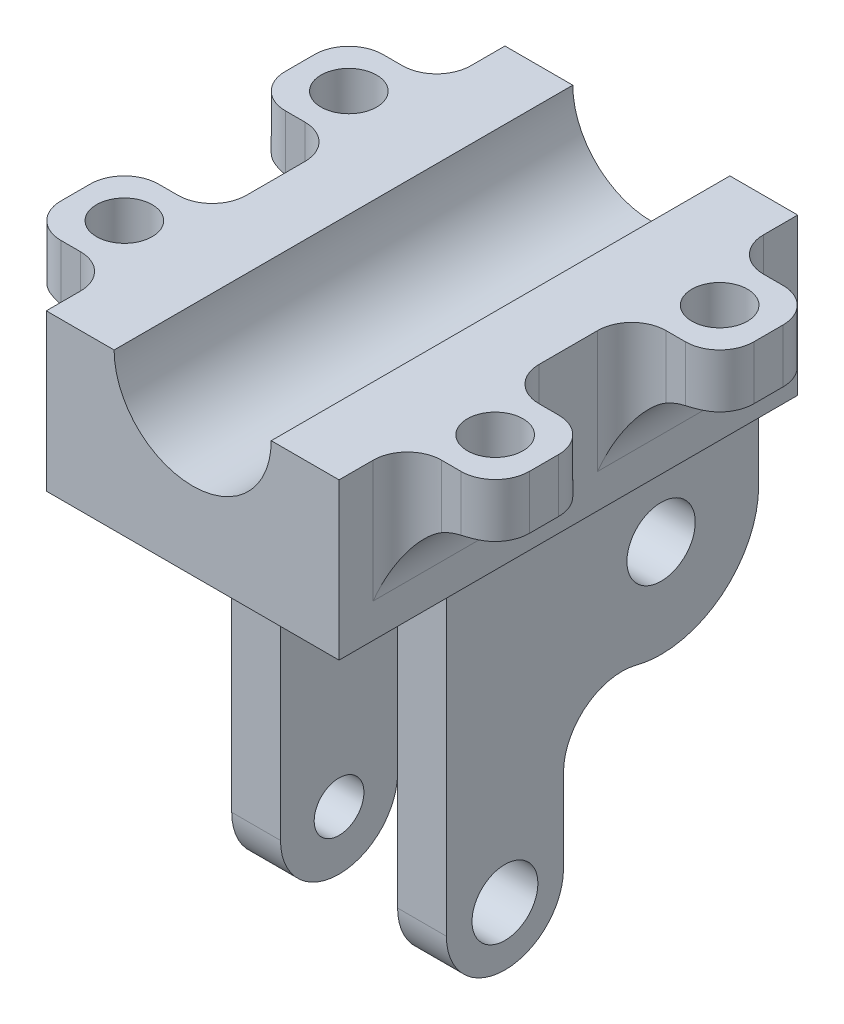
SolidWorks part; units mm, degrees
ref_plane "Front Plane" through (0, 0, 0) normal (0, 0, 1) x (1, 0, 0)
ref_plane "Top Plane" through (0, 0, 0) normal (0, 1, 0) x (1, 0, 0)
ref_plane "Right Plane" through (0, 0, 0) normal (1, 0, 0) x (0, 0, -1)
sketch "Sketch1" plane through (0, 0, 0) normal (0, 0, 1) x (1, 0, 0)
  line L1 (-15, -16) -> (15, -16)
  line L2 (-15, -16) -> (-15, 16)
  line L3 (-15, 16) -> (15, 16)
  line L4 (15, -16) -> (15, 16)
  line L5 (-15, -16) -> (15, 16) construction
  line L6 (-15, 16) -> (15, -16) construction
  circle A0 centre (0, 0) radius 8.05
  dimension "D1" = 16.1
  dimension "D2" = 30
  dimension "D3" = 32
extrude "Boss-Extrude1" add sketch "Sketch1" along normal blind 47
sketch "Sketch3" plane through (0, 0, 0) normal (0, 0, 1) x (1, 0, 0)
  line L0 (-15, 16) -> (-15, -16) construction
  line L1 (-15, 0) -> (15, 0)
  line L2 (-15, 0) -> (-15, 16)
  line L3 (-15, 16) -> (15, 16)
  line L4 (15, 0) -> (15, 16)
extrude "Cut-Extrude1" cut sketch "Sketch3" along normal through all both and the other way through all
sketch "Sketch4" plane through (0, 0, 0) normal (0, 1, 0) x (1, 0, 0)
  line L0 (15, -47) -> (15, 0) construction
  line L1 (15, -7) -> (24, -7)
  line L2 (15, -7) -> (15, -17)
  line L3 (15, -17) -> (24, -17)
  line L4 (24, -7) -> (24, -17)
  line L5 (8.05, 0) -> (15, 0) construction
  line L7 (0, 0) -> (0, 5.7091) construction
  line L15 (-24, -7) -> (-24, -17)
  line L16 (-15, -17) -> (-24, -17)
  line L17 (-15, -7) -> (-15, -17)
  line L18 (-15, -7) -> (-24, -7)
  line L19 (15, -23.5) -> (24.2871, -23.5) construction
  line L20 (-24, -40) -> (-24, -30)
  line L21 (-15, -30) -> (-24, -30)
  line L22 (-15, -40) -> (-15, -30)
  line L23 (-15, -40) -> (-24, -40)
  line L24 (15, -40) -> (15, -30)
  line L25 (15, -40) -> (24, -40)
  line L26 (15, -30) -> (24, -30)
  line L27 (24, -40) -> (24, -30)
  circle A0 centre (19, -12) radius 2.85
  circle A1 centre (19, -35) radius 2.85
  circle A2 centre (-19, -12) radius 2.85
  circle A3 centre (-19, -35) radius 2.85
  point P8 (24, -12)
  point P33 (24, -35)
  dimension "D4" = 5.7
  dimension "D1" = 10
  dimension "D2" = 9
  dimension "D3" = 7
extrude "Boss-Extrude2" add sketch "Sketch4" against normal blind 5.5
fillet "Fillet1" radius 3.5 16 edges at (15, -2.75, 17) (24, -2.75, 17) (24, -2.75, 7) (15, -2.75, 7) (-24, -2.75, 7) (-24, -2.75, 17) (-15, -2.75, 7) (-15, -2.75, 17) (24, -2.75, 30) (15, -2.75, 30) (24, -2.75, 40) (15, -2.75, 40) (-15, -2.75, 30) (-24, -2.75, 30) (-24, -2.75, 40) (-15, -2.75, 40)
fillet "Fillet2" radius 7 4 edges at (-15, -5.5, 12) (-15, -5.5, 35) (15, -5.5, 35) (15, -5.5, 12)
sketch "Sketch5" plane through (0, -16, 0) normal (0, -1, 0) x (1, 0, 0)
  line L0 (-15, 0) -> (15, 0) construction
  line L1 (-6, 0) -> (-11, 0)
  line L2 (-6, 0) -> (-6, 20)
  line L3 (-6, 20) -> (-11, 20)
  line L4 (-11, 0) -> (-11, 20)
  line L5 (-15, 47) -> (-15, 0) construction
  line L6 (0, 0) -> (0, 17.1726) construction
  line L7 (11, 0) -> (11, 20)
  line L8 (6, 20) -> (11, 20)
  line L9 (6, 0) -> (6, 20)
  line L10 (6, 0) -> (11, 0)
  dimension "D1" = 4
  dimension "D2" = 5
  dimension "D3" = 20
  dimension "D4" = 12
extrude "Boss-Extrude3" add sketch "Sketch5" along normal blind 20
sketch "Sketch6" plane through (11, 0, 0) normal (1, 0, 0) x (0, 0, -1)
  circle A0 centre (-10, -26) radius 3.5
  dimension "D1" = 7
extrude "Cut-Extrude2" cut sketch "Sketch6" against normal through all both and the other way through all
fillet "Fillet3" radius 10 4 edges at (-8.5, -36, 0) (-8.5, -36, 20) (8.5, -36, 20) (8.5, -36, 0)
fillet "Fillet4" radius 4 2 edges at (-11, -16, 10) (11, -16, 10)
sketch "Sketch7" plane through (0, -16, 0) normal (0, -1, 0) x (1, 0, 0)
  line L0 (0, 0) -> (0, 21.1072) construction
  line L1 (-11, 20) -> (-6, 20)
  line L2 (-11, 20) -> (-11, 32)
  line L3 (-11, 32) -> (-6, 32)
  line L4 (-6, 20) -> (-6, 32)
  line L5 (6, 20) -> (6, 32)
  line L6 (11, 32) -> (6, 32)
  line L7 (11, 20) -> (11, 32)
  line L8 (11, 20) -> (6, 20)
  dimension "D1" = 12
extrude "Boss-Extrude4" add sketch "Sketch7" along normal blind 40
fillet "Fillet5" radius 6 4 edges at (8.5, -56, 20) (-8.5, -56, 20) (-8.5, -56, 32) (8.5, -56, 32)
fillet "Fillet7" radius 4 2 edges at (-11, -16, 26) (11, -16, 26)
sketch "Sketch9" plane through (11, 0, 0) normal (1, 0, 0) x (0, 0, -1)
  circle A0 centre (-26, -50) radius 3.375
  dimension "D1" = 6.75
extrude "Cut-Extrude3" cut sketch "Sketch9" against normal up to surface (5 mm away) and the other way through all up to face at (6, -26, 6.5)
sketch "Sketch10" plane through (-11, 0, 0) normal (-1, 0, 0) x (0, 0, 1)
  circle A0 centre (26, -50) radius 2.55
  dimension "D1" = 5.1
extrude "Cut-Extrude4" cut sketch "Sketch10" against normal up to surface (5 mm away) and the other way through all up to face at (-6, -26, 13.5)
fillet "Fillet8" radius 6 2 edges at (-8.5, -26, 20) (8.5, -26, 20)
